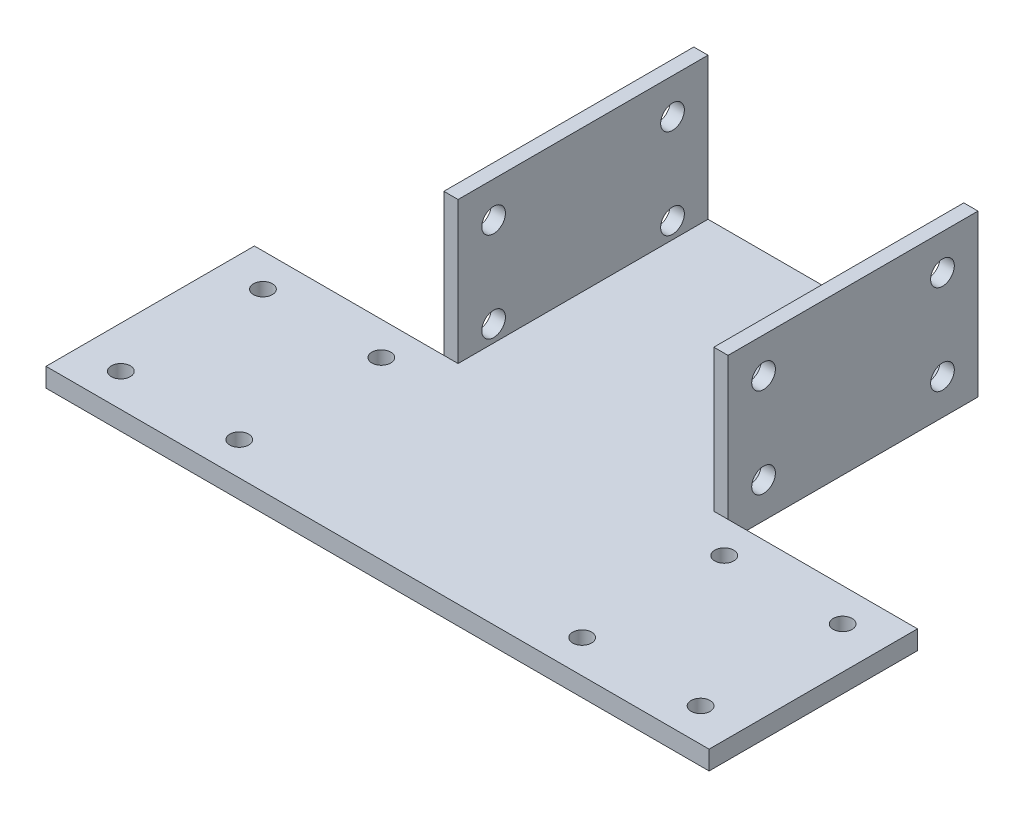
SolidWorks part; units mm, degrees
ref_plane "前视基准面" through (0, 0, 0) normal (0, 0, 1) x (1, 0, 0)
ref_plane "上视基准面" through (0, 0, 0) normal (0, 1, 0) x (1, 0, 0)
ref_plane "右视基准面" through (0, 0, 0) normal (1, 0, 0) x (0, 0, -1)
other "Configuration Table"
sketch "草图1" plane through (0, 0, 0) normal (0, 1, 0) x (1, 0, 0)
  line L0 (70, 0) -> (70, 61.6509) construction
  line L1 (0, 0) -> (140, 0)
  line L2 (0, 0) -> (0, 44)
  line L3 (0, 44) -> (140, 44)
  line L4 (140, 0) -> (140, 44)
  line L5 (43, 44) -> (43, 96.7734)
  line L6 (40, 44) -> (100, 44)
  line L7 (40, 44) -> (40, 96.7734)
  line L8 (40, 96.7734) -> (100, 96.7734)
  line L9 (100, 44) -> (100, 96.7734)
  line L10 (97, 96.7734) -> (97, 44)
  circle A0 centre (8.8, 7) radius 2
  circle A1 centre (8.8, 37) radius 2
  circle A2 centre (33.8, 37) radius 2
  circle A3 centre (33.8, 7) radius 2
  circle A4 centre (131.2, 37) radius 2
  circle A5 centre (131.2, 7) radius 2
  circle A6 centre (106.2, 7) radius 2
  circle A7 centre (106.2, 37) radius 2
  dimension "D3" = 4
  dimension "D4" = 4
  dimension "D5" = 4
  dimension "D6" = 4
  dimension "D7" = 8.8
  dimension "D8" = 8.8
  dimension "D9" = 7
  dimension "D10" = 7
  dimension "D12" = 7
  dimension "D13" = 25
  dimension "D14" = 25
  dimension "D1" = 140
  dimension "D2" = 44
  dimension "D11" = 7
  dimension "D15" = 60
  dimension "D16" = 30
  dimension "D17" = 3
  dimension "D18" = 3
extrude "凸台-拉伸1" add sketch "草图1" along normal blind 4 contours L1 L0 L3 L2 A0 A1 A2 A3 | L0 L1 L4 L3 L6 A6 A4 A5 A7 | L10 L8 L5 L3 L6 region at (35.2273, 0, -22) region at (104.7727, 0, -22) region at (70, 0, -70.3867)
extrude "凸台-拉伸2" add sketch "草图1<3>" along normal blind 34 contours L8 L10 L6 L9 | L8 L7 L3 L5 region at (41.5, 0, -70.3867) region at (98.5, 0, -70.3867)
sketch "草图1<3>" plane through (0, 0, 0) normal (0, 1, 0) x (1, 0, 0) same geometry as "草图1"
sketch "草图2" plane through (0, 0, 0) normal (1, 0, 0) x (0, 0, -1)
  line L0 (44, 0) -> (96.7734, 0) construction
  line L1 (96.7734, 34) -> (96.7734, 0) construction
  line L2 (44, 34) -> (44, 4) construction
  line L3 (44, 34) -> (96.7734, 34) construction
  circle A0 centre (51.5, 7.5) radius 2.5
  circle A1 centre (89.2734, 7.5) radius 2.5
  circle A2 centre (89.2734, 26.5) radius 2.5
  circle A3 centre (51.5, 26.5) radius 2.5
  dimension "D1" = 5
  dimension "D2" = 5
  dimension "D3" = 5
  dimension "D4" = 5
  dimension "D5" = 7.5
  dimension "D6" = 7.5
  dimension "D7" = 7.5
  dimension "D8" = 7.5
  dimension "D9" = 7.5
  dimension "D10" = 7.5
  dimension "D12" = 7.5
  dimension "D11" = 7.5
extrude "切除-拉伸1" cut sketch "草图2" against normal through all both and the other way through all
